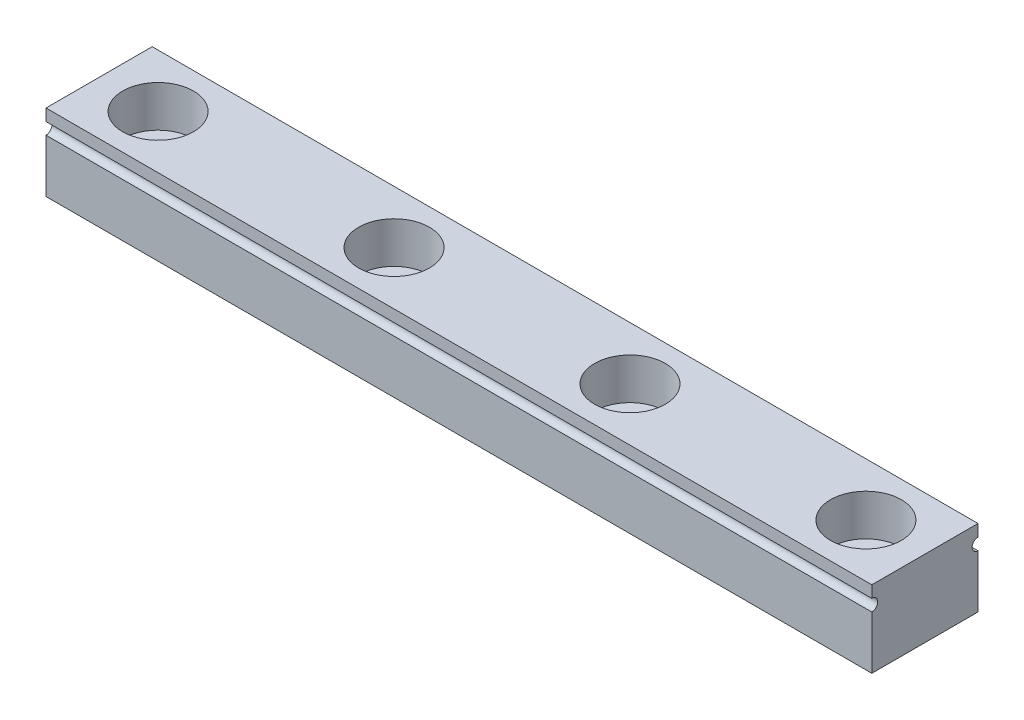
SolidWorks part; units mm, degrees
material "Plain Carbon Steel"
ref_plane "Front Plane" through (0, 0, 0) normal (0, 0, 1) x (1, 0, 0)
ref_plane "Top Plane" through (0, 0, 0) normal (0, 1, 0) x (1, 0, 0)
ref_plane "Right Plane" through (0, 0, 0) normal (1, 0, 0) x (0, 0, -1)
sketch "Sketch1" plane through (0, 0, 0) normal (1, 0, 0) x (0, 0, -1)
  line L1 (-4.5, 3.25) -> (4.5, 3.25)
  line L2 (-4.5, 3.25) -> (-4.5, -3.25)
  line L3 (-4.5, -3.25) -> (4.5, -3.25)
  line L4 (4.5, 3.25) -> (4.5, -3.25)
  line L5 (-4.5, 3.25) -> (4.5, -3.25) construction
  line L6 (-4.5, -3.25) -> (4.5, 3.25) construction
  circle A0 centre (-4.5, 1.75) radius 0.5
  circle A1 centre (4.5, 1.75) radius 0.5
  point P0 (0, 0)
  dimension "D3" = 1
  dimension "D4" = 1.5
  dimension "D1" = 6.5
  dimension "D2" = 9
extrude "it is 6.5mm, dont fuckin change" add sketch "Sketch1" along normal blind 70 contours A1 L4 L1 L2 A0 L3 region at (0, -0.0238, 0)
sketch "Sketch2" plane through (0, 3.25, 0) normal (0, 1, 0) x (1, 0, 0)
  line L1 (25, 0) -> (35, 4.5) construction
  line L2 (70, 4.5) -> (0, 4.5) construction
  line L3 (35, 4.5) -> (45, 0) construction
  circle A0 centre (5, 0) radius 1.5
  circle A1 centre (25, 0) radius 1.5
  circle A2 centre (45, 0) radius 1.5
  circle A3 centre (65, 0) radius 1.5
  dimension "D2" = 3
  dimension "D4" = 20
  dimension "D3" = 4
extrude "Cut-Extrude1" cut sketch "Sketch2" against normal through all
sketch "Sketch3" plane through (0, 3.25, 0) normal (0, 1, 0) x (1, 0, 0)
  circle A0 centre (5, 0) radius 3
  circle A1 centre (25, 0) radius 3
  circle A2 centre (45, 0) radius 3
  circle A15 centre (65, 0) radius 3
  dimension "D1" = 6
  dimension "D3" = 20
  dimension "D2" = 4
extrude "Cut-Extrude2" cut sketch "Sketch3" against normal blind 3.5
equation "\"l\" = 70'length(7.5*2+20*n) n is an interger"
equation "\"D1@it is 6.5mm, dont fuckin change\" = \"l\""
equation "\"D2@Sketch3\"=(\"l\"-15)/20+1"
equation "\"D3@Sketch2\"=(\"l\"-15)/20+1"
